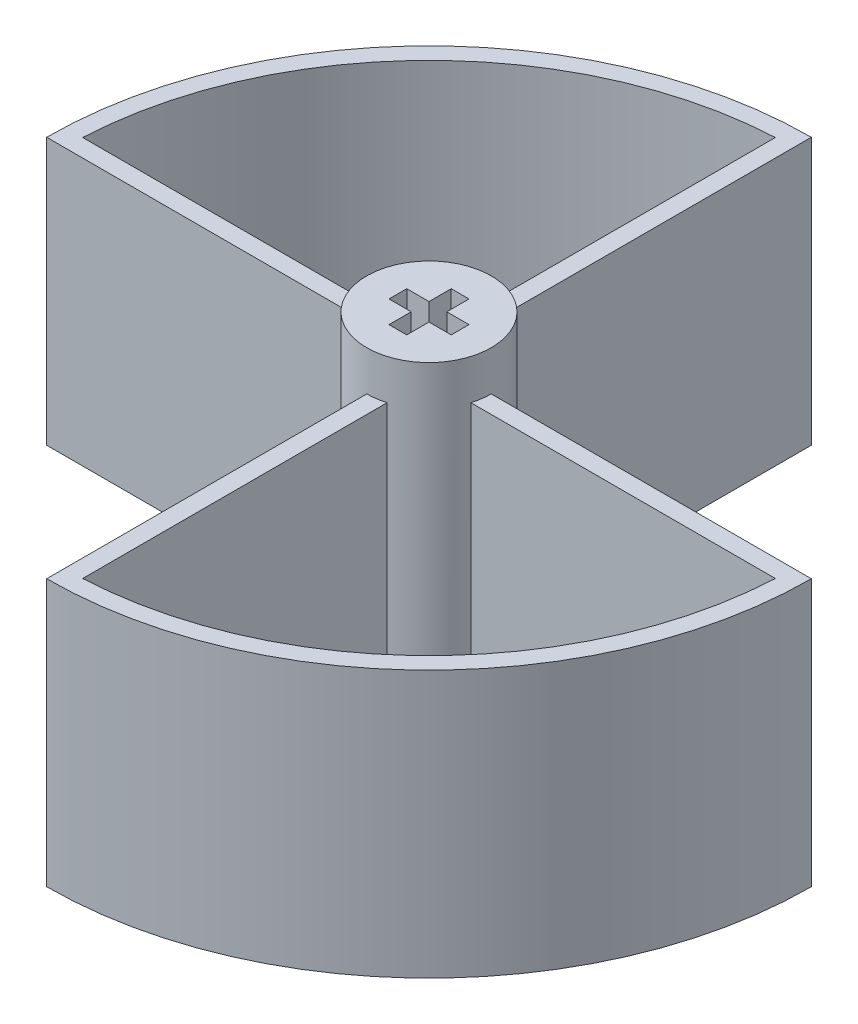
SolidWorks part; units mm, degrees
ref_plane "前视基准面" through (0, 0, 0) normal (0, 0, 1) x (1, 0, 0)
ref_plane "上视基准面" through (0, 0, 0) normal (0, 1, 0) x (1, 0, 0)
ref_plane "右视基准面" through (0, 0, 0) normal (1, 0, 0) x (0, 0, -1)
sketch "草图1" plane through (0, 0, 0) normal (0, 1, 0) x (1, 0, 0)
  line L7 (0, 7) -> (0, 43)
  line L8 (7, 0) -> (43, 0)
  line L9 (-7, 0) -> (-43, 0)
  line L10 (0, -7) -> (0, -43)
  arc A2 (0, 43) -> (-43, 0) centre (0, 0) ccw
  arc A4 (0, -43) -> (43, 0) centre (0, 0) ccw
  arc A5 (-7, 0) -> (0, -7) centre (0, 0) ccw
  arc A6 (7, 0) -> (0, 7) centre (0, 0) ccw
  dimension "D1" = 86
  dimension "D2" = 7
extrude "凸台-拉伸1" add sketch "草图1" along normal blind 30
sketch "草图2" plane through (0, 30, 0) normal (0, 1, 0) x (1, 0, 0)
  line L0 (1, -1) -> (1, -3.5)
  line L1 (-1, 3.5) -> (1, 3.5)
  line L2 (-1, 3.5) -> (-1, 1)
  line L3 (-1, -3.5) -> (1, -3.5)
  line L4 (1, 3.5) -> (1, 1)
  line L5 (-1, 3.5) -> (1, -3.5) construction
  line L6 (-1, -3.5) -> (1, 3.5) construction
  line L7 (-3.5, 1) -> (-1, 1)
  line L8 (-3.5, 1) -> (-3.5, -1)
  line L9 (-3.5, -1) -> (-1, -1)
  line L10 (3.5, 1) -> (3.5, -1)
  line L11 (-3.5, 1) -> (3.5, -1) construction
  line L12 (-3.5, -1) -> (3.5, 1) construction
  line L13 (-1, -1) -> (-1, -3.5)
  line L14 (1, 1) -> (3.5, 1)
  line L16 (1, -1) -> (3.5, -1)
  point P0 (0, 0)
  point P6 (0, 0)
  dimension "D1" = 2
  dimension "D2" = 7
extrude "切除-拉伸1" cut sketch "草图2" against normal through all
shell "抽壳1" thickness 2 removed face at (0, 30, 0)
sketch "草图3" plane through (0, 30, 0) normal (0, 1, 0) x (1, 0, 0)
  line L28 (-3.5, 1) -> (-1, 1)
  line L29 (-1, 1) -> (-1, 3.5)
  line L30 (-1, 3.5) -> (1, 3.5)
  line L31 (1, 3.5) -> (1, 1)
  line L32 (1, 1) -> (3.5, 1)
  line L33 (3.5, 1) -> (3.5, -1)
  line L34 (3.5, -1) -> (1, -1)
  line L35 (1, -1) -> (1, -3.5)
  line L36 (1, -3.5) -> (-1, -3.5)
  line L37 (-1, -3.5) -> (-1, -1)
  line L38 (-1, -1) -> (-3.5, -1)
  line L39 (-3.5, -1) -> (-3.5, 1)
  circle A0 centre (0, 0) radius 7
extrude "凸台-拉伸2" add sketch "草图3" along normal blind 4.5 and the other way blind 34.5
